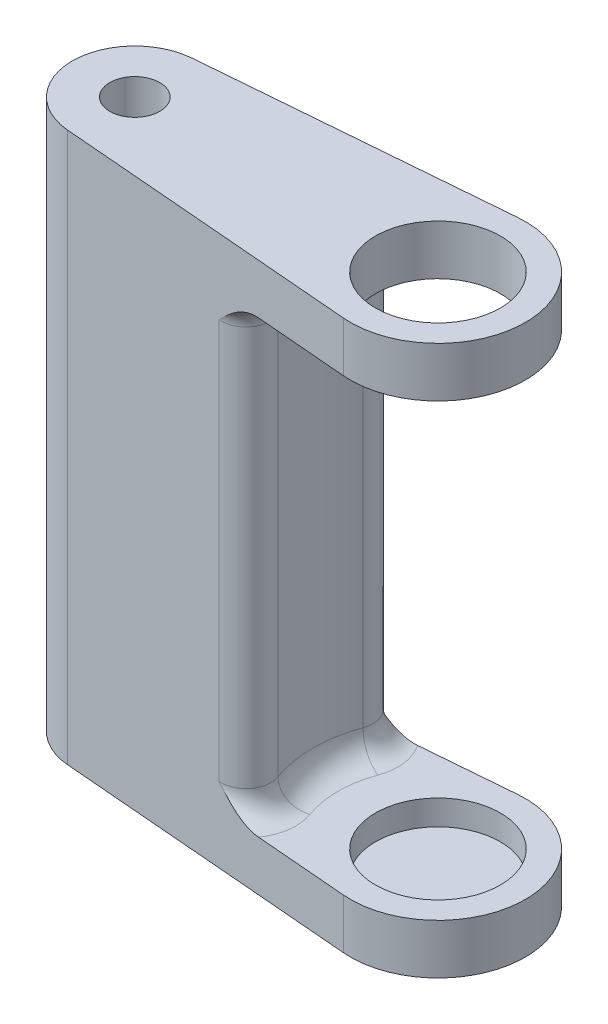
SolidWorks part; units mm, degrees
ref_plane "Front Plane" through (0, 0, 0) normal (0, 0, 1) x (1, 0, 0)
ref_plane "Top Plane" through (0, 0, 0) normal (0, 1, 0) x (1, 0, 0)
ref_plane "Right Plane" through (0, 0, 0) normal (1, 0, 0) x (0, 0, -1)
sketch "Sketch1" plane through (0, 0, 0) normal (0, 1, 0) x (1, 0, 0)
  line L0 (-0.206, 2.4915) -> (11.8455, 3.4881)
  line L1 (-0.206, -2.4915) -> (11.8455, -3.4881)
  circle A4 centre (0, 0) radius 1
  circle A5 centre (0, 0) radius 2.5
  circle A6 centre (12.134, 0) radius 2.5
  circle A7 centre (12.134, 0) radius 5
  circle A8 centre (12.134, 0) radius 3.5
  point P10 (11.3064, -3.3426)
  point P13 (0, 0)
  dimension "D1" = 2
  dimension "D2" = 5
  dimension "D3" = 5
  dimension "D4" = 10
  dimension "D5" = 7
extrude "Boss-Extrude5" add sketch "Sketch1" along normal blind 2 contours A5 A4 | A7 L0 A5 L1 | A8 L0 A7 L1 | A8 A6 region at (4.7478, 0, 0) region at (1.6455, 0, -1.7871) region at (8.512, 0, 0) region at (14.4376, 0, -2.502)
extrude "Boss-Extrude6" add sketch "Sketch1<7>" along normal blind 22 contours A5 A4 | A7 L0 A5 L1 region at (4.7478, 0, 0) region at (1.6455, 0, -1.7871)
sketch "Sketch1<7>" plane through (0, 0, 0) normal (0, 1, 0) x (1, 0, 0) same geometry as "Sketch1"
extrude "Boss-Extrude7" add sketch "Sketch1<8>" against normal blind 2 from surface contours A8 L0 A7 L1 | A8 A6 region at (8.512, 0, 0) region at (14.4376, 0, -2.502) starting at face at (0, 22, 1)
sketch "Sketch1<8>" plane through (0, 0, 0) normal (0, 1, 0) x (1, 0, 0) same geometry as "Sketch1"
extrude "Boss-Extrude8" add sketch "Sketch1<9>" along normal blind 1 contours A6 region at (12.134, 0, 0)
sketch "Sketch1<9>" plane through (0, 0, 0) normal (0, 1, 0) x (1, 0, 0) same geometry as "Sketch1"
fillet "Fillet3" radius 1 2 edges at (8.2869, 11, -3.1938) (8.2869, 11, 3.1938)
fillet "Fillet1" radius 1 6 edges at (7.134, 20, 0) (7.134, 2, 0) (7.2864, 20, -2.6496) (7.2864, 20, 2.6496) (7.2864, 2, 2.6496) (7.2864, 2, -2.6496)
